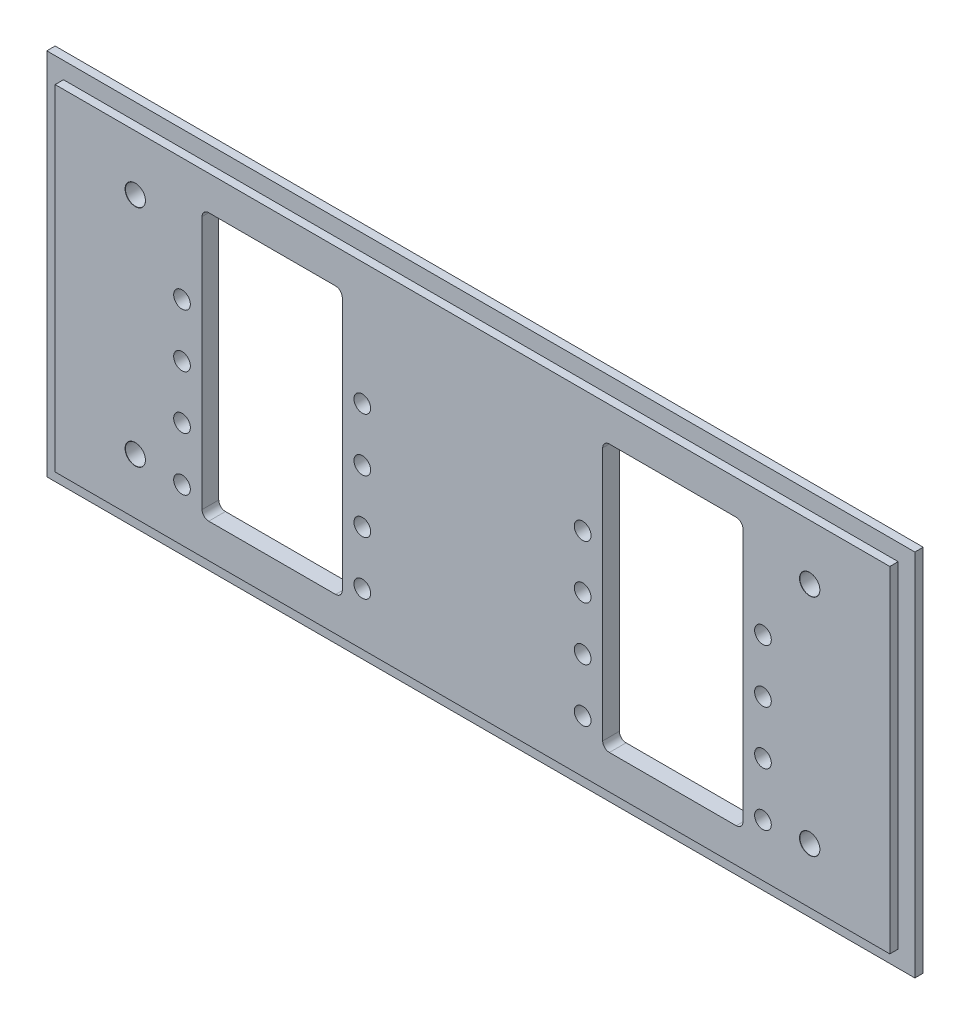
SolidWorks part; units mm, degrees
ref_plane "Plano frontal" through (0, 0, 0) normal (0, 0, 1) x (1, 0, 0)
ref_plane "Plano superior" through (0, 0, 0) normal (0, 1, 0) x (1, 0, 0)
ref_plane "Plano direito" through (0, 0, 0) normal (1, 0, 0) x (0, 0, -1)
sketch "Esboço1" plane through (0, 0, 0) normal (0, 0, 1) x (1, 0, 0)
  line L1 (-63.2916, 33.3513) -> (66.7084, 33.3513)
  line L2 (-63.2916, 33.3513) -> (-63.2916, -21.8987)
  line L3 (-63.2916, -21.8987) -> (66.7084, -21.8987)
  line L4 (66.7084, 33.3513) -> (66.7084, -21.8987)
  dimension "D1" = 130
  dimension "D2" = 55.25
extrude "Ressalto-extrusão1" add sketch "Esboço1" along normal blind 2.5
sketch "Esboço2" plane through (0, 0, 2.5) normal (0, 0, 1) x (1, 0, 0)
  line L0 (1.7084, 33.3513) -> (1.7084, -21.8987) construction
  line L1 (66.7084, 33.3513) -> (-63.2916, 33.3513) construction
  line L2 (-63.2916, -21.8987) -> (66.7084, -21.8987) construction
  line L11 (-54.581, 33.3513) -> (-54.581, -21.8987) construction
  line L13 (-63.2916, 33.3513) -> (66.7084, 33.3513)
  line L14 (-63.2916, 33.3513) -> (-63.2916, -21.8987)
  line L15 (-63.2916, -21.8987) -> (66.7084, -21.8987)
  line L16 (66.7084, 33.3513) -> (66.7084, -21.8987)
  line L17 (-60.7916, 30.8513) -> (64.2084, 30.8513)
  line L18 (-60.7916, 30.8513) -> (-60.7916, -19.3987)
  line L19 (-60.7916, -19.3987) -> (64.2084, -19.3987)
  line L20 (64.2084, 30.8513) -> (64.2084, -19.3987)
  dimension "D1" = 2.5
  dimension "D2" = 2.5
  dimension "D3" = 2.5
  dimension "D4" = 2.5
extrude "Corte-extrusão1" cut sketch "Esboço2" against normal blind 1.25
sketch "Esboço3" plane through (0, 0, 2.5) normal (0, 0, 1) x (1, 0, 0)
  line L0 (-48.7916, 30.8513) -> (-48.7916, -19.3987) construction
  line L1 (64.2084, 30.8513) -> (-60.7916, 30.8513) construction
  line L2 (-60.7916, -19.3987) -> (64.2084, -19.3987) construction
  line L3 (-60.7916, 30.8513) -> (-60.7916, -19.3987) construction
  line L4 (1.7084, 30.8513) -> (1.7084, -19.3987) construction
  line L5 (-60.7916, 5.7263) -> (1.7084, 5.7263) construction
  circle A0 centre (-48.7916, 22.5513) radius 2.75
  circle A1 centre (-48.7916, -11.0987) radius 2.75
  circle A2 centre (52.2084, -11.0987) radius 2.75
  circle A3 centre (52.2084, 22.5513) radius 2.75
  point P14 (-48.7916, 19.8013)
  dimension "D2" = 11.05
  dimension "D1" = 12
hole_wizard "Furos-guia com Ø3.0mm2" positions "Esboço4" profile "Esboço5" hole size "Ø3.0" standard "ISO" end condition through all
sketch "Esboço4" plane through (0, 0, 2.5) normal (0, 0, 1) x (1, 0, 0)
  point P0 (-48.7916, 22.5513)
  point P3 (-48.7916, -11.0987)
  point P6 (52.2084, -11.0987)
  point P9 (52.2084, 22.5513)
sketch "Esboço5" plane through (-48.7916, 22.5513, 2.5) normal (1, 0, 0) x (0, -1, 0)
  line L0 (0, 0) -> (0, 2.5)
  line L1 (0, 2.5) -> (1.5, 2.5)
  line L2 (1.5, 2.5) -> (1.5, 0.025)
  line L3 (1.5, 0.025) -> (1.525, 0)
  line L5 (1.525, 0) -> (0, 0)
  line L6 (-1.5, 0.025) -> (-1.525, 0) construction
  line L11 (0, -6.35) -> (0, 107.95) construction
  dimension "Thru Hole Dia." = 3
  dimension "Thru Hole Depth" = 2.5
  dimension "Near C'Sink Dia." = 3.05
  dimension "Near C'Sink Angle" = 90
sketch "Sketch1" plane through (0, 0, 2.5) normal (0, 0, 1) x (1, 0, 0)
  line L0 (47.7084, 5.7263) -> (-44.2916, 5.7263) construction
  line L1 (-44.2916, 5.7263) -> (-44.2916, 30.7263) construction
  line L2 (-44.2916, 30.7263) -> (-12.2916, 30.7263) construction
  line L3 (-12.2916, 30.7263) -> (-12.2916, -19.2737) construction
  line L4 (-12.2916, -19.2737) -> (-44.2916, -19.2737) construction
  line L5 (-44.2916, -19.2737) -> (-44.2916, 5.7263) construction
  line L6 (-28.2916, 30.7263) -> (-28.2916, -19.2737) construction
  line L7 (-44.2916, 30.7263) -> (-41.7916, 30.7263) construction
  line L8 (-41.7916, 30.7263) -> (-41.7916, -19.2737) construction
  line L9 (-18.5916, -13.2737) -> (-23.9916, -13.2737) construction
  line L10 (-17.7916, -14.2737) -> (-38.7916, -14.2737)
  line L11 (1.7084, -19.3987) -> (1.7084, 30.8513) construction
  line L12 (-17.7916, -14.2737) -> (-17.7916, 25.7304)
  line L13 (-17.7916, 25.7304) -> (-38.7916, 25.7304)
  line L14 (-38.7916, -14.2737) -> (-38.7916, 25.7304)
  line L15 (-33.0416, -17.7737) -> (-23.5416, -17.7737) construction
  line L16 (-18.2916, -6.5737) -> (-18.2916, -12.9737) construction
  line L18 (45.2084, 30.7263) -> (45.2084, -19.2737) construction
  line L19 (47.7084, 30.7263) -> (45.2084, 30.7263) construction
  line L20 (31.7084, 30.7263) -> (31.7084, -19.2737) construction
  line L21 (47.7084, -19.2737) -> (47.7084, 5.7263) construction
  line L22 (15.7084, -19.2737) -> (47.7084, -19.2737) construction
  line L23 (15.7084, 30.7263) -> (15.7084, -19.2737) construction
  line L24 (47.7084, 30.7263) -> (15.7084, 30.7263) construction
  line L25 (47.7084, 5.7263) -> (47.7084, 30.7263) construction
  line L26 (42.2084, -14.2737) -> (42.2084, 25.7304)
  line L27 (21.2084, 25.7304) -> (42.2084, 25.7304)
  line L28 (21.2084, -14.2737) -> (21.2084, 25.7304)
  line L29 (21.2084, -14.2737) -> (42.2084, -14.2737)
  circle A1 centre (-41.7916, 12.4763) radius 1.25
  circle A2 centre (-41.7916, 4.4763) radius 1.25
  circle A3 centre (-41.7916, -3.5237) radius 1.25
  circle A4 centre (-41.7916, -11.5237) radius 1.25
  circle A5 centre (-14.7916, 12.4763) radius 1.25
  circle A6 centre (-14.7916, -11.5237) radius 1.25
  circle A7 centre (-14.7916, 4.4763) radius 1.25
  circle A8 centre (-14.7916, -3.5237) radius 1.25
  circle A11 centre (-28.2916, 19.2263) radius 4 construction
  circle A12 centre (18.2084, -3.5237) radius 1.25
  circle A13 centre (18.2084, 4.4763) radius 1.25
  circle A14 centre (18.2084, -11.5237) radius 1.25
  circle A15 centre (18.2084, 12.4763) radius 1.25
  circle A16 centre (45.2084, -11.5237) radius 1.25
  circle A17 centre (45.2084, -3.5237) radius 1.25
  circle A18 centre (45.2084, 4.4763) radius 1.25
  circle A19 centre (45.2084, 12.4763) radius 1.25
  point P35 (-21.2916, -13.2737)
  point P38 (-28.2916, -17.7737)
  point P39 (-28.2916, -14.2737)
  point P55 (1.7084, 5.7263)
  dimension "D5" = 0.5
  dimension "D8" = 2.5
  dimension "D11" = 6.5041
  dimension "D1" = 46
  dimension "D2" = 50
  dimension "D3" = 32
  dimension "D4" = 1
  dimension "D6" = 2.5
  dimension "D7" = 18.25
  dimension "D10" = 8
  dimension "D9" = 4
extrude "Cut-Extrude1" cut sketch "Sketch1" against normal blind 10
fillet "Filete1" radius 1 8 edges at (42.2084, -14.2737, 1.25) (42.2084, 25.7304, 1.25) (21.2084, 25.7304, 1.25) (21.2084, -14.2737, 1.25) (-17.7916, -14.2737, 1.25) (-17.7916, 25.7304, 1.25) (-38.7916, 25.7304, 1.25) (-38.7916, -14.2737, 1.25)
